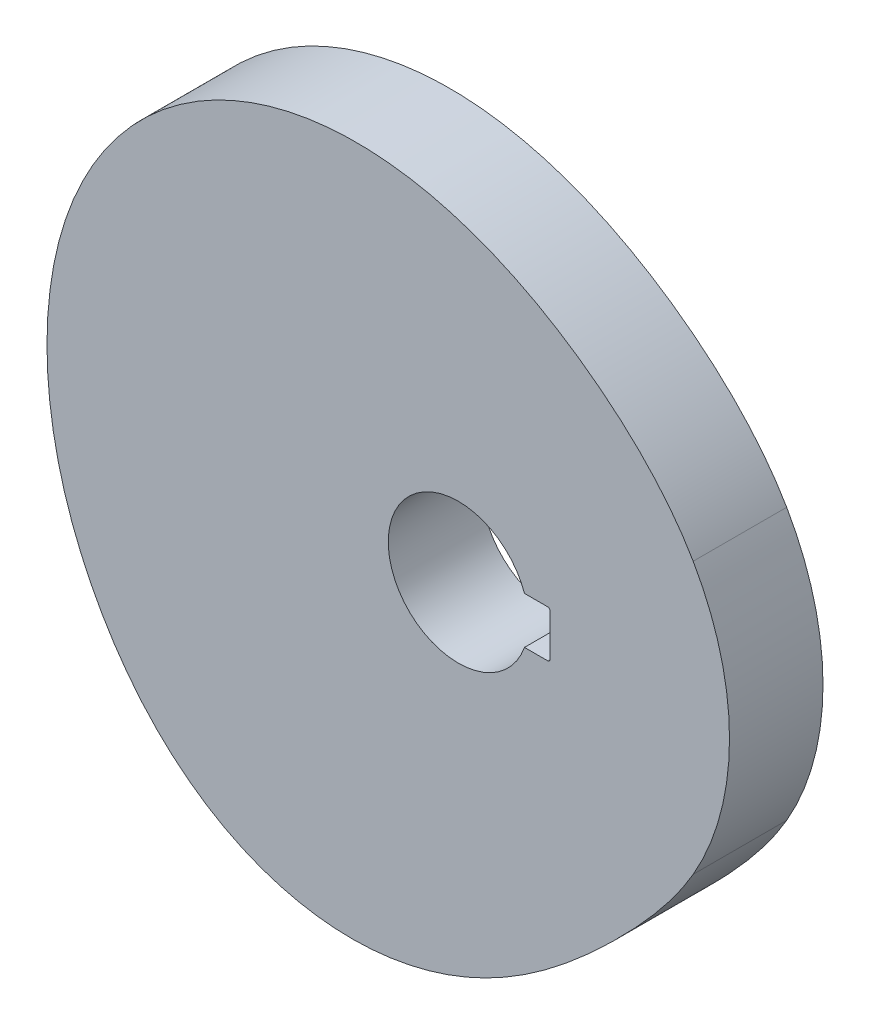
SolidWorks part; units mm, degrees
material "Plain Carbon Steel"
ref_plane "Front Plane" through (0, 0, 0) normal (0, 0, 1) x (1, 0, 0)
ref_plane "Top Plane" through (0, 0, 0) normal (0, 1, 0) x (1, 0, 0)
ref_plane "Right Plane" through (0, 0, 0) normal (1, 0, 0) x (0, 0, -1)
sketch "Displacement Sketch" plane through (0, 0, 0) normal (0, 0, 1) x (1, 0, 0)
  line L0 (0, 15) -> (0, 0) construction
  line L1 (0, 0) -> (47.1239, 0) construction
  line L2 (3.927, 0) -> (3.927, 15) construction
  line L3 (23.5619, 0) -> (23.5619, 15) construction
  line L4 (27.4889, 0) -> (27.4889, 15) construction
  line L5 (43.1969, 0) -> (43.1969, 15) construction
  line L6 (47.1239, 0) -> (47.1239, 15) construction
  line L7 (0, 0) -> (3.927, 0)
  line L8 (27.4889, 15) -> (23.5619, 15)
  line L9 (43.1969, 0) -> (47.1239, 0)
  spline S0 degree 4 poles (1.962, -0.0967) (2.0251, -0.0879) (2.1497, -0.0715) (2.3802, -0.0441) (2.7786, -0.0172) (3.1491, -0.0023) (3.8234, 0.0011) (4.1519, -0.0013) (4.7825, 0.0037) (5.2973, 0.0292) (5.8993, 0.0828) (6.4992, 0.198) (7.1843, 0.4092) (7.8229, 0.6945) (8.5028, 1.0958) (9.2434, 1.664) (10.1514, 2.5325) (11.1276, 3.6845) (12.1583, 5.0983) (13.2223, 6.6951) (14.2666, 8.3049) (15.3308, 9.9017) (16.361, 11.3155) (17.3382, 12.4675) (18.2447, 13.336) (18.9876, 13.9042) (19.6636, 14.3055) (20.2354, 14.5584) (20.6913, 14.7109) (21.0546, 14.8041) (21.3223, 14.8591) (21.5625, 14.8998) (21.7937, 14.9296) (22.0274, 14.9566) (22.3642, 14.9781) (22.6856, 14.9963) (23.3417, 15.0013) (23.6628, 14.9989) (24.3418, 15.0023) (24.7635, 15.0193) (25.1747, 15.049) (25.3985, 15.0791) (25.5259, 15.0967) knots 0 0 0 0 0 0.008159 0.016318 0.032637 0.048955 0.065274 0.0892 0.101163 0.113126 0.142767 0.163984 0.185201 0.206418 0.236195 0.268021 0.309045 0.372696 0.436348 0.5 0.563652 0.627304 0.690955 0.731979 0.763805 0.793582 0.814799 0.836016 0.846625 0.857233 0.864643 0.872053 0.879463 0.886874 0.898837 0.9108 0.934726 0.951045 0.967363 0.983682 1 1 1 1 1 construction
  spline S1 degree 4 poles (3.927, 0) (4.0838, 0) (4.3123, 0) (4.7825, 0.0037) (5.2973, 0.0292) (5.8993, 0.0828) (6.4992, 0.198) (7.1843, 0.4092) (7.8229, 0.6945) (8.5028, 1.0958) (9.2434, 1.664) (10.1514, 2.5325) (11.1276, 3.6845) (12.1583, 5.0983) (13.2223, 6.6951) (14.2666, 8.3049) (15.3308, 9.9017) (16.361, 11.3155) (17.3382, 12.4675) (18.2447, 13.336) (18.9876, 13.9042) (19.6636, 14.3055) (20.2354, 14.5584) (20.6913, 14.7109) (21.0546, 14.8041) (21.3223, 14.8591) (21.5625, 14.8998) (21.7937, 14.9296) (22.0274, 14.9566) (22.3642, 14.9781) (22.6856, 14.9963) (23.1748, 15) (23.4052, 15) (23.5619, 15) knots 0.065274 0.065274 0.065274 0.065274 0.065274 0.0892 0.101163 0.113126 0.142767 0.163984 0.185201 0.206418 0.236195 0.268021 0.309045 0.372696 0.436348 0.5 0.563652 0.627304 0.690955 0.731979 0.763805 0.793582 0.814799 0.836016 0.846625 0.857233 0.864643 0.872053 0.879463 0.886874 0.898837 0.9108 0.934726 0.934726 0.934726 0.934726 0.934726
  spline S2 degree 4 poles (25.917, 15.0967) (25.9672, 15.0879) (26.0664, 15.0716) (26.2503, 15.0442) (26.5692, 15.0173) (26.8684, 15.0023) (27.398, 14.9989) (27.6696, 15.0012) (28.1638, 14.9965) (28.4688, 14.9775) (28.7956, 14.949) (29.0691, 14.9044) (29.3652, 14.8416) (29.6303, 14.7623) (29.8895, 14.6683) (30.1363, 14.5572) (30.3781, 14.4298) (30.708, 14.2278) (31.1287, 13.9151) (31.7056, 13.3799) (32.4321, 12.5171) (33.1948, 11.3999) (33.9837, 10.0588) (34.759, 8.6207) (35.5133, 7.1717) (36.2737, 5.7258) (37.0683, 4.2981) (37.8437, 3.0586) (38.5964, 2.0494) (39.2866, 1.3197) (39.8479, 0.8516) (40.4053, 0.501) (40.8925, 0.2823) (41.3433, 0.149) (41.8164, 0.0573) (42.2412, 0.0166) (42.6103, 0.0017) (43.0977, -0.0005) (43.3551, 0.0006) (43.8251, -0.0023) (44.1115, -0.0173) (44.4386, -0.0442) (44.6184, -0.0716) (44.7185, -0.0879) (44.7693, -0.0967) knots 0 0 0 0 0 0.007472 0.014944 0.029888 0.044832 0.059777 0.081272 0.09202 0.102768 0.114604 0.126441 0.136767 0.147094 0.15742 0.167746 0.178072 0.188398 0.21612 0.247099 0.297177 0.359134 0.421092 0.48305 0.545008 0.606966 0.668924 0.730882 0.766656 0.797635 0.820922 0.841574 0.866069 0.878735 0.891402 0.915813 0.928018 0.940223 0.955168 0.970112 0.985056 0.992528 1 1 1 1 1 construction
  spline S3 degree 4 poles (27.4889, 15) (27.6137, 15) (27.7971, 15) (28.1638, 14.9965) (28.4688, 14.9775) (28.7956, 14.949) (29.0691, 14.9044) (29.3652, 14.8416) (29.6303, 14.7623) (29.8895, 14.6683) (30.1363, 14.5572) (30.3781, 14.4298) (30.708, 14.2278) (31.1287, 13.9151) (31.7056, 13.3799) (32.4321, 12.5171) (33.1948, 11.3999) (33.9837, 10.0588) (34.759, 8.6207) (35.5133, 7.1717) (36.2737, 5.7258) (37.0683, 4.2981) (37.8437, 3.0586) (38.5964, 2.0494) (39.2866, 1.3197) (39.8479, 0.8516) (40.4053, 0.501) (40.8925, 0.2823) (41.3433, 0.149) (41.8164, 0.0573) (42.2412, 0.0166) (42.6103, 0.0017) (42.9834, 0) (43.1261, 0) (43.1969, 0) knots 0.059777 0.059777 0.059777 0.059777 0.059777 0.081272 0.09202 0.102768 0.114604 0.126441 0.136767 0.147094 0.15742 0.167746 0.178072 0.188398 0.21612 0.247099 0.297177 0.359134 0.421092 0.48305 0.545008 0.606966 0.668924 0.730882 0.766656 0.797635 0.820922 0.841574 0.866069 0.878735 0.891402 0.915813 0.928018 0.940223 0.940223 0.940223 0.940223 0.940223
  dimension "D1" = 15
  dimension "D2" = 47.1239
  dimension "D3" = 3.927
  dimension "D4" = 19.635
  dimension "D5" = 3.927
  dimension "D6" = 15.708
  dimension "D7" = 3.927
sketch "Velocity Sketch" plane through (0, 0, 0) normal (0, 0, 1) x (1, 0, 0)
  line L0 (0, -15) -> (0, -65) construction
  line L1 (0, -40) -> (47.1239, -40) construction
  line L2 (3.927, -15) -> (3.927, -65) construction
  line L3 (23.5619, -15) -> (23.5619, -65) construction
  line L4 (27.4889, -15) -> (27.4889, -65) construction
  line L5 (43.1969, -15) -> (43.1969, -65) construction
  line L6 (47.1239, -15) -> (47.1239, -65) construction
  line L7 (0, -40) -> (3.927, -40)
  line L8 (23.5619, -40) -> (27.4889, -40)
  line L9 (43.1969, -40) -> (47.1239, -40)
  spline S0 degree 4 number of poles 82 (1.9635, -38.9057) -> (25.5254, -38.9057) construction
  spline S1 degree 4 poles (3.927, -40) (3.9591, -40) (4.0069, -39.9984) (4.0914, -39.9931) (4.2047, -39.9788) (4.3113, -39.9585) (4.4273, -39.9287) (4.5497, -39.8882) (4.6855, -39.8341) (4.8338, -39.7637) (5.0005, -39.6692) (5.2228, -39.5203) (5.4703, -39.3234) (5.7369, -39.0742) (6.0182, -38.7713) (6.2635, -38.4767) (6.4789, -38.1966) (6.7119, -37.8755) (6.9601, -37.5119) (7.2378, -37.08) (7.6188, -36.4531) (8.0578, -35.69) (8.695, -34.5334) (9.3923, -33.2428) (10.1106, -31.9631) (10.8521, -30.798) (11.4447, -29.9912) (12.0701, -29.306) (12.6823, -28.8165) (13.3594, -28.5265) (13.9982, -28.5224) (14.4931, -28.6816) (14.9938, -28.9673) (15.4821, -29.3759) (16.0352, -29.9801) (16.6301, -30.7877) (17.3726, -31.9534) (18.0917, -33.2337) (18.7893, -34.5249) (19.4267, -35.6821) (19.8657, -36.4456) (20.2468, -37.073) (20.5641, -37.567) (20.8732, -38.0148) (21.1744, -38.4151) (21.4671, -38.7672) (21.7491, -39.0713) (22.0564, -39.3589) (22.3514, -39.5861) (22.6045, -39.7396) (22.8026, -39.8338) (22.9386, -39.888) (23.0611, -39.9286) (23.1771, -39.9584) (23.2842, -39.9788) (23.3789, -39.9907) (23.4581, -39.9971) (23.5136, -39.9995) (23.5459, -40) (23.5619, -40) knots 0.064432 0.064432 0.064432 0.064432 0.064432 0.068544 0.0706 0.072656 0.076768 0.08088 0.083926 0.086973 0.093066 0.099159 0.105252 0.116762 0.128271 0.13978 0.15129 0.159464 0.167638 0.183987 0.200336 0.216684 0.249382 0.282079 0.347474 0.380171 0.412868 0.435887 0.458906 0.483278 0.499726 0.516191 0.528398 0.540605 0.563699 0.586794 0.619507 0.652221 0.717647 0.750361 0.783074 0.799431 0.815787 0.832144 0.8485 0.860048 0.871595 0.883143 0.89469 0.906897 0.913 0.916052 0.919104 0.92322 0.927336 0.929394 0.931452 0.93351 0.935568 0.935568 0.935568 0.935568 0.935568
  spline S2 degree 4 number of poles 99 (25.9181, -41.3678) -> (44.7677, -41.3678) construction
  spline S3 degree 4 number of poles 73 (27.4889, -40) -> (43.1969, -40)
  point P15 (23.5619, -40)
  point P27 (43.1969, -40)
  point P28 (3.927, -40)
  point P35 (27.4889, -40)
  dimension "D1" = 50
  dimension "D2" = 15
  dimension "D3" = 47.1239
sketch "Acceleration Sketch" plane through (0, 0, 0) normal (0, 0, 1) x (1, 0, 0)
  line L0 (0, -80) -> (0, -130) construction
  line L1 (0, -15) -> (0, -65) construction
  line L2 (3.927, -80) -> (3.927, -130) construction
  line L3 (23.5619, -80) -> (23.5619, -130) construction
  line L4 (27.4889, -80) -> (27.4889, -130) construction
  line L5 (43.1969, -80) -> (43.1969, -130) construction
  line L6 (47.1239, -80) -> (47.1239, -130) construction
  line L7 (0, -105) -> (47.1239, -105) construction
  spline S0 degree 4 number of poles 85 (2.572, -110.7775) -> (24.917, -99.2225) construction
  spline S1 degree 4 number of poles 69 (3.927, -105) -> (23.5619, -105)
  spline S2 degree 4 number of poles 85 (26.4484, -96.3102) -> (44.2375, -113.6898) construction
  spline S3 degree 4 number of poles 77 (27.4889, -105) -> (43.1969, -105)
  point P30 (3.927, -105)
  dimension "D1" = 15
sketch "Cam Profile Sketch" plane through (0, 0, 0) normal (0, 0, 1) x (1, 0, 0)
  line L0 (-49, 0) -> (-93, 0) construction
  line L1 (-49, 0) -> (-23.8853, 14.5) construction
  line L3 (-49, 0) -> (-87.1051, -22) construction
  line L4 (-23.8853, -14.5) -> (-49, 0) construction
  circle A1 centre (-49, 0) radius 29 construction
  arc A2 (-93, 0) -> (-87.1051, -22) centre (-49, 0) ccw
  arc A3 (-23.8853, -14.5) -> (-23.8853, 14.5) centre (-49, 0) ccw
  spline S0 degree 4 number of poles 84 (-21.0816, 7.4807) -> (-91.9863, -9.6611) construction
  spline S1 degree 4 poles (-23.8853, 14.5) (-23.9328, 14.5824) (-24.0277, 14.7445) (-24.2319, 15.0878) (-24.4645, 15.4634) (-24.7034, 15.8366) (-24.9512, 16.2123) (-25.2035, 16.5831) (-25.4607, 16.9499) (-25.7512, 17.3524) (-26.2677, 18.0453) (-27.1324, 19.1368) (-28.4165, 20.6093) (-30.1456, 22.3683) (-31.9522, 24.0003) (-33.682, 25.4157) (-35.2829, 26.6203) (-36.7346, 27.637) (-38.214, 28.6) (-39.7256, 29.5117) (-41.2684, 30.3695) (-43.2348, 31.3707) (-45.6528, 32.452) (-48.5535, 33.523) (-51.6032, 34.3581) (-54.3423, 34.8797) (-57.1097, 35.211) (-59.8951, 35.3457) (-63.056, 35.2217) (-66.5557, 34.7132) (-69.9807, 33.8313) (-73.2889, 32.5802) (-76.4387, 30.9712) (-79.4088, 29.0105) (-82.1582, 26.7166) (-84.6496, 24.1145) (-86.8505, 21.2354) (-88.7264, 18.1351) (-90.2072, 14.9786) (-91.2012, 12.1859) (-91.847, 9.8314) (-92.2209, 8.1094) (-92.439, 6.9089) (-92.5993, 5.859) (-92.7156, 4.9622) (-92.7998, 4.1755) (-92.8596, 3.4999) (-92.9013, 2.9365) (-92.9298, 2.4854) (-92.9534, 2.0327) (-92.9723, 1.5812) (-92.9864, 1.1389) (-92.9957, 0.6708) (-92.9992, 0.2901) (-93, 0.0959) (-93, 0) knots 0.066188 0.066188 0.066188 0.066188 0.066188 0.070099 0.07401 0.07792 0.081831 0.085742 0.089653 0.093564 0.097475 0.103059 0.11981 0.142146 0.165611 0.189076 0.204719 0.220116 0.235513 0.25091 0.266306 0.281703 0.2971 0.327893 0.358686 0.38948 0.407291 0.425102 0.455895 0.486688 0.517482 0.548275 0.579069 0.609862 0.640655 0.672207 0.70376 0.735312 0.766864 0.798416 0.82521 0.838607 0.852004 0.859892 0.86778 0.875668 0.883556 0.8875 0.891444 0.895388 0.899332 0.903276 0.90722 0.911164 0.915108 0.915108 0.915108 0.915108 0.915108
  spline S2 degree 4 number of poles 81 (-21.5114, -8.9316) -> (-90.4641, -14.9011) construction
  spline S3 degree 4 poles (-23.8853, -14.5) (-23.9228, -14.565) (-23.9986, -14.695) (-24.1533, -14.9565) (-24.3405, -15.2639) (-24.5245, -15.5577) (-24.7154, -15.8558) (-24.9096, -16.152) (-25.204, -16.5908) (-25.5555, -17.0963) (-26.07, -17.8075) (-26.6555, -18.5744) (-27.2016, -19.2598) (-27.9845, -20.2063) (-28.905, -21.2718) (-29.9727, -22.445) (-31.1919, -23.7204) (-32.3132, -24.8484) (-33.3264, -25.8344) (-34.356, -26.8033) (-35.4027, -27.7536) (-36.4677, -28.6835) (-37.5521, -29.5906) (-38.6574, -30.4723) (-40.0665, -31.5389) (-41.5142, -32.5534) (-43.2999, -33.6987) (-45.4952, -34.9391) (-47.7646, -36.0414) (-50.4458, -37.085) (-53.2075, -37.8928) (-55.9852, -38.4418) (-58.8021, -38.7298) (-61.634, -38.7457) (-64.4538, -38.4832) (-67.3037, -37.9274) (-69.7768, -37.1729) (-71.8775, -36.3239) (-73.6249, -35.4667) (-75.324, -34.5176) (-76.9536, -33.4513) (-78.5066, -32.2766) (-79.9784, -31.0034) (-80.9649, -30.0639) (-81.7785, -29.2267) (-82.4351, -28.5089) (-82.9475, -27.9232) (-83.4441, -27.3299) (-83.925, -26.73) (-84.391, -26.1233) (-84.8413, -25.5121) (-85.2807, -24.8903) (-85.7062, -24.2635) (-86.123, -23.6232) (-86.4733, -23.0634) (-86.7658, -22.58) (-86.9827, -22.2109) (-87.0648, -22.0699) (-87.1051, -22) knots 0.065589 0.065589 0.065589 0.065589 0.065589 0.069408 0.073227 0.077046 0.080865 0.084684 0.088503 0.092322 0.103716 0.111291 0.126441 0.134017 0.141592 0.16438 0.187294 0.202569 0.217845 0.233121 0.248396 0.263672 0.278948 0.294223 0.309499 0.324775 0.355326 0.370602 0.401153 0.433708 0.464259 0.49481 0.525362 0.555913 0.586464 0.617016 0.647567 0.6812 0.698016 0.714832 0.731649 0.765281 0.782098 0.798914 0.81573 0.824138 0.832546 0.840955 0.849363 0.857574 0.865785 0.873997 0.882208 0.890419 0.898631 0.906842 0.910948 0.915054 0.915054 0.915054 0.915054 0.915054
  dimension "D2" = 29
  dimension "D1" = 49
  dimension "D3" = 44
  dimension "D4" = 30
  dimension "D6" = 30
  dimension "D7" = 30
  dimension "D8" = 180
extrude "Boss-Extrude1" add sketch "Cam Profile Sketch" along normal mid plane 10 contours S1 A2 S3 A3
sketch "Sketch2" plane through (0, 0, 0) normal (0, 0, 1) x (1, 0, 0)
  circle A0 centre (-49, 0) radius 7.5
  dimension "D1" = 15
extrude "Cut-Extrude2" cut sketch "Sketch2" against normal up to next and the other way up to next
sketch "Sketch3" plane through (0, 0, 0) normal (0, 0, 1) x (1, 0, 0)
  line L0 (-49, 0) -> (-41.5, 0) construction
  line L2 (-41.9289, 2.5) -> (-39.2, 2.5)
  line L3 (-41.9289, 2.5) -> (-41.9289, -2.5)
  line L4 (-41.9289, -2.5) -> (-39.2, -2.5)
  line L5 (-39.2, 2.5) -> (-39.2, -2.5)
  circle A0 centre (-49, 0) radius 7.5 construction
  dimension "D1" = 5
  dimension "D2" = 2.3
extrude "Cut-Extrude3" cut sketch "Sketch3" against normal up to next and the other way up to next
fillet "Fillet1" radius 0.25 2 edges at (-39.2, -2.5, 0) (-39.2, 2.5, 0)
sketch "Sketch6" plane through (0, 0, 0) normal (0, 0, 1) x (1, 0, 0)
  arc A4 (-14.359, -20) -> (-14.359, 20) centre (-49, 0) ccw
  arc A6 (-14.359, -20) -> (-14.359, 20) centre (-49, 0) ccw construction
  spline S2 degree 3 poles (-104, 0) (-104, -9.7106) (-101.4867, -19.0904) (-96.6314, -27.5) knots 0 0 0 0 1 1 1 1 weights 1 0.977284 0.977284 1
  spline S3 degree 3 poles (-104, 0) (-104, -9.7106) (-101.4867, -19.0904) (-96.6314, -27.5) knots 0 0 0 0 1 1 1 1 weights 1 0.977284 0.977284 1
  spline S4 degree 3 poles (-2121.3509, -2107.8884) (-90.1041, -268.0393) (38.8532, -41.6264) (-20.5996, 28.4116) (-22.4507, 30.2678) (-24.9339, 32.4444) (-25.4387, 32.8721) (-26.4578, 33.7074) (-26.9729, 34.1158) (-28.5344, 35.3143) (-29.5968, 36.0777) (-32.8466, 38.2639) (-35.096, 39.5839) (-38.6055, 41.3389) (-39.7981, 41.886) (-41.6241, 42.6453) (-42.2401, 42.8885) (-43.4792, 43.3515) (-44.1013, 43.5708) (-47.2243, 44.6062) (-49.7632, 45.239) (-53.6363, 45.8756) (-54.9381, 46.0356) (-57.5645, 46.2456) (-58.895, 46.2951) (-62.8479, 46.27) (-65.4489, 46.0259) (-69.2986, 45.3166) (-70.5732, 45.0228) (-72.4716, 44.493) (-73.1022, 44.3015) (-74.3588, 43.8881) (-74.9855, 43.6658) (-78.0732, 42.4898) (-80.4238, 41.3359) (-83.7745, 39.2932) (-84.8621, 38.5601) (-86.9774, 36.9869) (-88.0088, 36.143) (-90.9518, 33.4994) (-92.7313, 31.5775) (-95.1366, 28.464) (-95.8941, 27.3876) (-96.9631, 25.7141) (-97.3081, 25.1465) (-97.9694, 24.0026) (-98.2864, 23.425) (-99.8056, 20.5097) (-100.8105, 18.0901) (-101.8163, 14.9617) (-102.0048, 14.3308) (-102.3568, 13.0586) (-102.5205, 12.4162) (-102.9719, 10.4812) (-103.2193, 9.185) (-136.6485, -212.174) (1276.4183, -601.8103) (-3010.0616, -323.1715) knots -2.072484 -2.072484 -2.072484 -2.072484 0.0625 0.0625 0.125 0.125 0.140625 0.140625 0.15625 0.15625 0.1875 0.1875 0.25 0.25 0.28125 0.28125 0.296875 0.296875 0.3125 0.3125 0.375 0.375 0.40625 0.40625 0.4375 0.4375 0.5 0.5 0.53125 0.53125 0.546875 0.546875 0.5625 0.5625 0.625 0.625 0.65625 0.65625 0.6875 0.6875 0.75 0.75 0.78125 0.78125 0.796875 0.796875 0.8125 0.8125 0.875 0.875 0.890625 0.890625 0.90625 0.90625 0.9375 0.9375 6.218529 6.218529 6.218529 6.218529 only from (-14.359, 20) to (-104, 0)
  spline S5 degree 3 poles (-2669.4706, -1511.9471) (347.9627, 724.0401) (-201.4987, 75.5733) (-88.246, -38.3286) (-87.4685, -39.057) (-85.8573, -40.4573) (-85.0312, -41.1228) (-82.492, -43.0154) (-80.7182, -44.1392) (-77.9326, -45.6129) (-76.9833, -46.0686) (-75.5269, -46.6973) (-75.036, -46.8976) (-74.0433, -47.2796) (-73.5402, -47.4616) (-71.0112, -48.3187) (-68.96, -48.8314) (-64.8037, -49.5242) (-62.6986, -49.7043) (-60.0329, -49.7174) (-59.4973, -49.7092) (-58.4318, -49.6719) (-57.9009, -49.6427) (-56.3137, -49.5242) (-55.2629, -49.404) (-52.1315, -48.9244) (-50.0719, -48.446) (-47.0233, -47.4984) (-46.0126, -47.1432) (-44.0327, -46.3685) (-43.06, -45.9479) (-40.1903, -44.5927) (-38.3418, -43.5645) (-35.6544, -41.8576) (-34.7712, -41.2599) (-33.0389, -40.0196) (-32.1924, -39.3789) (-29.7036, -37.4036) (-28.1117, -36.0161) (-25.027, -33.1371) (-23.5326, -31.6474) (-20.6447, -28.562) (-19.2514, -26.9647) (30.4783, 36.9799) (-58.8139, 192.9555) (-2354.1483, 1850.1458) knots -4.584283 -4.584283 -4.584283 -4.584283 0.125 0.125 0.15625 0.15625 0.1875 0.1875 0.25 0.25 0.28125 0.28125 0.296875 0.296875 0.3125 0.3125 0.375 0.375 0.4375 0.4375 0.453125 0.453125 0.46875 0.46875 0.5 0.5 0.5625 0.5625 0.59375 0.59375 0.625 0.625 0.6875 0.6875 0.71875 0.71875 0.75 0.75 0.8125 0.8125 0.875 0.875 0.9375 0.9375 3.249827 3.249827 3.249827 3.249827 only from (-96.6314, -27.5) to (-14.359, -20)
  spline S6 degree 3 poles (-14.359, 20) (-15.6869, 22.2999) (-17.2178, 24.4276) (-20.5996, 28.4116) (-22.4507, 30.2678) (-24.9339, 32.4444) (-25.4387, 32.8721) (-26.4578, 33.7074) (-26.9729, 34.1158) (-28.5344, 35.3143) (-29.5968, 36.0777) (-32.8466, 38.2639) (-35.096, 39.5839) (-38.6055, 41.3389) (-39.7981, 41.886) (-41.6241, 42.6453) (-42.2401, 42.8885) (-43.4792, 43.3515) (-44.1013, 43.5708) (-47.2243, 44.6062) (-49.7632, 45.239) (-53.6363, 45.8756) (-54.9381, 46.0356) (-57.5645, 46.2456) (-58.895, 46.2951) (-62.8479, 46.27) (-65.4489, 46.0259) (-69.2986, 45.3166) (-70.5732, 45.0228) (-72.4716, 44.493) (-73.1022, 44.3015) (-74.3588, 43.8881) (-74.9855, 43.6658) (-78.0732, 42.4898) (-80.4238, 41.3359) (-83.7745, 39.2932) (-84.8621, 38.5601) (-86.9774, 36.9869) (-88.0088, 36.143) (-90.9518, 33.4994) (-92.7313, 31.5775) (-95.1366, 28.464) (-95.8941, 27.3876) (-96.9631, 25.7141) (-97.3081, 25.1465) (-97.9694, 24.0026) (-98.2864, 23.425) (-99.8056, 20.5097) (-100.8105, 18.0901) (-101.8163, 14.9617) (-102.0048, 14.3308) (-102.3568, 13.0586) (-102.5205, 12.4162) (-102.9719, 10.4812) (-103.2193, 9.185) (-103.8093, 5.2785) (-104, 2.6504) (-104, 0) knots 0 0 0 0 0.0625 0.0625 0.125 0.125 0.140625 0.140625 0.15625 0.15625 0.1875 0.1875 0.25 0.25 0.28125 0.28125 0.296875 0.296875 0.3125 0.3125 0.375 0.375 0.40625 0.40625 0.4375 0.4375 0.5 0.5 0.53125 0.53125 0.546875 0.546875 0.5625 0.5625 0.625 0.625 0.65625 0.65625 0.6875 0.6875 0.75 0.75 0.78125 0.78125 0.796875 0.796875 0.8125 0.8125 0.875 0.875 0.890625 0.890625 0.90625 0.90625 0.9375 0.9375 1 1 1 1 construction
  spline S7 degree 3 poles (-96.6314, -27.5) (-94.4988, -31.1938) (-91.9789, -34.5743) (-88.246, -38.3286) (-87.4685, -39.057) (-85.8573, -40.4573) (-85.0312, -41.1228) (-82.492, -43.0154) (-80.7182, -44.1392) (-77.9326, -45.6129) (-76.9833, -46.0686) (-75.5269, -46.6973) (-75.036, -46.8976) (-74.0433, -47.2796) (-73.5402, -47.4616) (-71.0112, -48.3187) (-68.96, -48.8314) (-64.8037, -49.5242) (-62.6986, -49.7043) (-60.0329, -49.7174) (-59.4973, -49.7092) (-58.4318, -49.6719) (-57.9009, -49.6427) (-56.3137, -49.5242) (-55.2629, -49.404) (-52.1315, -48.9244) (-50.0719, -48.446) (-47.0233, -47.4984) (-46.0126, -47.1432) (-44.0327, -46.3685) (-43.06, -45.9479) (-40.1903, -44.5927) (-38.3418, -43.5645) (-35.6544, -41.8576) (-34.7712, -41.2599) (-33.0389, -40.0196) (-32.1924, -39.3789) (-29.7036, -37.4036) (-28.1117, -36.0161) (-25.027, -33.1371) (-23.5326, -31.6474) (-20.6447, -28.562) (-19.2514, -26.9647) (-16.6339, -23.5989) (-15.4257, -21.8476) (-14.359, -20) knots 0 0 0 0 0.125 0.125 0.15625 0.15625 0.1875 0.1875 0.25 0.25 0.28125 0.28125 0.296875 0.296875 0.3125 0.3125 0.375 0.375 0.4375 0.4375 0.453125 0.453125 0.46875 0.46875 0.5 0.5 0.5625 0.5625 0.59375 0.59375 0.625 0.625 0.6875 0.6875 0.71875 0.71875 0.75 0.75 0.8125 0.8125 0.875 0.875 0.9375 0.9375 1 1 1 1 construction
  dimension "D1" = 11
sketch3d "3DSketch1"
  arc A0 (-23.8853, 14.5, 0) -> (-23.8853, -14.5, 0) centre (-49, 0, 0) ccw
  arc A1 (-23.8853, 14.5, 0) -> (-23.8853, -14.5, 0) centre (-49, 0, 0) ccw
  arc A2 (-87.1051, -22, 0) -> (-93, 0, 0) centre (-49, 0, 0) ccw
  arc A3 (-87.1051, -22, 0) -> (-93, 0, 0) centre (-49, 0, 0) ccw
  spline S0 degree 4 poles (-1086.34, 1709.6276, 0) (-62.8727, -63.5271, 0) (-89.259, -18.1595, 0) (-87.6062, -21.1912, 0) (-86.4733, -23.0634, 0) (-86.123, -23.6232, 0) (-85.7062, -24.2635, 0) (-85.2807, -24.8903, 0) (-84.8413, -25.5121, 0) (-84.391, -26.1233, 0) (-83.925, -26.73, 0) (-83.4441, -27.3299, 0) (-82.9475, -27.9232, 0) (-82.4351, -28.5089, 0) (-81.7785, -29.2267, 0) (-80.9649, -30.0639, 0) (-79.9784, -31.0034, 0) (-78.5066, -32.2766, 0) (-76.9536, -33.4513, 0) (-75.324, -34.5176, 0) (-73.6249, -35.4667, 0) (-71.8775, -36.3239, 0) (-69.7768, -37.1729, 0) (-67.3037, -37.9274, 0) (-64.4538, -38.4832, 0) (-61.634, -38.7457, 0) (-58.8021, -38.7298, 0) (-55.9852, -38.4418, 0) (-53.2075, -37.8928, 0) (-50.4458, -37.085, 0) (-47.7646, -36.0414, 0) (-45.4952, -34.9391, 0) (-43.2999, -33.6987, 0) (-41.5142, -32.5534, 0) (-40.0665, -31.5389, 0) (-38.6574, -30.4723, 0) (-37.5521, -29.5906, 0) (-36.4677, -28.6835, 0) (-35.4027, -27.7536, 0) (-34.356, -26.8033, 0) (-33.3264, -25.8344, 0) (-32.3132, -24.8484, 0) (-31.1919, -23.7204, 0) (-29.9727, -22.445, 0) (-28.905, -21.2718, 0) (-27.9845, -20.2063, 0) (-27.2016, -19.2598, 0) (-26.6555, -18.5744, 0) (-26.07, -17.8075, 0) (-25.5555, -17.0963, 0) (-25.204, -16.5908, 0) (-24.9096, -16.152, 0) (-24.7154, -15.8558, 0) (-24.5245, -15.5577, 0) (-24.3405, -15.2639, 0) (-23.3608, -13.6549, 0) (-21.7979, -10.7579, 0) (-48.252, -56.0842, 0) (975.2221, 1717.4251, 0) knots -0.005181 -0.005181 -0.005181 -0.005181 -0.005181 0.069695 0.0738 0.082012 0.090223 0.098435 0.106646 0.114857 0.123069 0.13128 0.139688 0.148096 0.156504 0.164913 0.181729 0.198545 0.215361 0.248994 0.26581 0.282627 0.299443 0.333075 0.363627 0.394178 0.42473 0.455281 0.485832 0.516384 0.546935 0.57949 0.610041 0.625317 0.655868 0.671144 0.686419 0.701695 0.716971 0.732246 0.747522 0.762798 0.778073 0.793349 0.816263 0.839051 0.846626 0.854201 0.869352 0.876927 0.888321 0.89214 0.895959 0.899778 0.903597 0.907416 0.911235 0.979723 0.979723 0.979723 0.979723 0.979723 only from (-87.1051, -22, 0) to (-23.8853, -14.5, 0)
  spline S1 degree 4 poles (-87.1051, -22, 0) (-87.0648, -22.0699, 0) (-86.9827, -22.2109, 0) (-86.7658, -22.58, 0) (-86.4733, -23.0634, 0) (-86.123, -23.6232, 0) (-85.7062, -24.2635, 0) (-85.2807, -24.8903, 0) (-84.8413, -25.5121, 0) (-84.391, -26.1233, 0) (-83.925, -26.73, 0) (-83.4441, -27.3299, 0) (-82.9475, -27.9232, 0) (-82.4351, -28.5089, 0) (-81.7785, -29.2267, 0) (-80.9649, -30.0639, 0) (-79.9784, -31.0034, 0) (-78.5066, -32.2766, 0) (-76.9536, -33.4513, 0) (-75.324, -34.5176, 0) (-73.6249, -35.4667, 0) (-71.8775, -36.3239, 0) (-69.7768, -37.1729, 0) (-67.3037, -37.9274, 0) (-64.4538, -38.4832, 0) (-61.634, -38.7457, 0) (-58.8021, -38.7298, 0) (-55.9852, -38.4418, 0) (-53.2075, -37.8928, 0) (-50.4458, -37.085, 0) (-47.7646, -36.0414, 0) (-45.4952, -34.9391, 0) (-43.2999, -33.6987, 0) (-41.5142, -32.5534, 0) (-40.0665, -31.5389, 0) (-38.6574, -30.4723, 0) (-37.5521, -29.5906, 0) (-36.4677, -28.6835, 0) (-35.4027, -27.7536, 0) (-34.356, -26.8033, 0) (-33.3264, -25.8344, 0) (-32.3132, -24.8484, 0) (-31.1919, -23.7204, 0) (-29.9727, -22.445, 0) (-28.905, -21.2718, 0) (-27.9845, -20.2063, 0) (-27.2016, -19.2598, 0) (-26.6555, -18.5744, 0) (-26.07, -17.8075, 0) (-25.5555, -17.0963, 0) (-25.204, -16.5908, 0) (-24.9096, -16.152, 0) (-24.7154, -15.8558, 0) (-24.5245, -15.5577, 0) (-24.3405, -15.2639, 0) (-24.1533, -14.9565, 0) (-23.9986, -14.695, 0) (-23.9228, -14.565, 0) (-23.8853, -14.5, 0) knots 0.065589 0.065589 0.065589 0.065589 0.065589 0.069695 0.0738 0.082012 0.090223 0.098435 0.106646 0.114857 0.123069 0.13128 0.139688 0.148096 0.156504 0.164913 0.181729 0.198545 0.215361 0.248994 0.26581 0.282627 0.299443 0.333075 0.363627 0.394178 0.42473 0.455281 0.485832 0.516384 0.546935 0.57949 0.610041 0.625317 0.655868 0.671144 0.686419 0.701695 0.716971 0.732246 0.747522 0.762798 0.778073 0.793349 0.816263 0.839051 0.846626 0.854201 0.869352 0.876927 0.888321 0.89214 0.895959 0.899778 0.903597 0.907416 0.911235 0.915054 0.915054 0.915054 0.915054 0.915054
  spline S2 degree 4 poles (-92.388, -1999.3106, 0) (-92.7043, 49.3254, 0) (-92.9299, -4.8344, 0) (-93.0346, -1.2733, 0) (-92.9864, 1.1389, 0) (-92.9723, 1.5812, 0) (-92.9534, 2.0327, 0) (-92.9298, 2.4854, 0) (-92.9013, 2.9365, 0) (-92.8596, 3.4999, 0) (-92.7998, 4.1755, 0) (-92.7156, 4.9622, 0) (-92.5993, 5.859, 0) (-92.439, 6.9089, 0) (-92.2209, 8.1094, 0) (-91.847, 9.8314, 0) (-91.2012, 12.1859, 0) (-90.2072, 14.9786, 0) (-88.7264, 18.1351, 0) (-86.8505, 21.2354, 0) (-84.6496, 24.1145, 0) (-82.1582, 26.7166, 0) (-79.4088, 29.0105, 0) (-76.4387, 30.9712, 0) (-73.2889, 32.5802, 0) (-69.9807, 33.8313, 0) (-66.5557, 34.7132, 0) (-63.056, 35.2217, 0) (-59.8951, 35.3457, 0) (-57.1097, 35.211, 0) (-54.3423, 34.8797, 0) (-51.6032, 34.3581, 0) (-48.5535, 33.523, 0) (-45.6528, 32.452, 0) (-43.2348, 31.3707, 0) (-41.2684, 30.3695, 0) (-39.7256, 29.5117, 0) (-38.214, 28.6, 0) (-36.7346, 27.637, 0) (-35.2829, 26.6203, 0) (-33.682, 25.4157, 0) (-31.9522, 24.0003, 0) (-30.1456, 22.3683, 0) (-28.4165, 20.6093, 0) (-27.1324, 19.1368, 0) (-26.2677, 18.0453, 0) (-25.7512, 17.3524, 0) (-25.4607, 16.9499, 0) (-25.2035, 16.5831, 0) (-24.9512, 16.2123, 0) (-24.7034, 15.8366, 0) (-24.4645, 15.4634, 0) (-23.3636, 13.6856, 0) (-21.2575, 9.7985, 0) (-51.3705, 61.3574, 0) (975.0524, -1717.3854, 0) knots 0.000668 0.000668 0.000668 0.000668 0.000668 0.070132 0.074076 0.07802 0.081964 0.085908 0.089852 0.093796 0.09774 0.105628 0.113516 0.121404 0.129292 0.142689 0.156086 0.18288 0.214432 0.245984 0.277536 0.309089 0.340641 0.371434 0.402227 0.433021 0.463814 0.494608 0.525401 0.556194 0.574005 0.591816 0.62261 0.653403 0.684196 0.699593 0.71499 0.730386 0.745783 0.76118 0.776576 0.79222 0.815685 0.83915 0.861486 0.878237 0.883821 0.887732 0.891643 0.895554 0.899465 0.903376 0.907286 0.911197 0.973512 0.973512 0.973512 0.973512 0.973512 only from (-93, 0, 0) to (-23.8853, 14.5, 0)
  spline S3 degree 4 poles (-93, 0, 0) (-93, 0.0959, 0) (-92.9992, 0.2901, 0) (-92.9957, 0.6708, 0) (-92.9864, 1.1389, 0) (-92.9723, 1.5812, 0) (-92.9534, 2.0327, 0) (-92.9298, 2.4854, 0) (-92.9013, 2.9365, 0) (-92.8596, 3.4999, 0) (-92.7998, 4.1755, 0) (-92.7156, 4.9622, 0) (-92.5993, 5.859, 0) (-92.439, 6.9089, 0) (-92.2209, 8.1094, 0) (-91.847, 9.8314, 0) (-91.2012, 12.1859, 0) (-90.2072, 14.9786, 0) (-88.7264, 18.1351, 0) (-86.8505, 21.2354, 0) (-84.6496, 24.1145, 0) (-82.1582, 26.7166, 0) (-79.4088, 29.0105, 0) (-76.4387, 30.9712, 0) (-73.2889, 32.5802, 0) (-69.9807, 33.8313, 0) (-66.5557, 34.7132, 0) (-63.056, 35.2217, 0) (-59.8951, 35.3457, 0) (-57.1097, 35.211, 0) (-54.3423, 34.8797, 0) (-51.6032, 34.3581, 0) (-48.5535, 33.523, 0) (-45.6528, 32.452, 0) (-43.2348, 31.3707, 0) (-41.2684, 30.3695, 0) (-39.7256, 29.5117, 0) (-38.214, 28.6, 0) (-36.7346, 27.637, 0) (-35.2829, 26.6203, 0) (-33.682, 25.4157, 0) (-31.9522, 24.0003, 0) (-30.1456, 22.3683, 0) (-28.4165, 20.6093, 0) (-27.1324, 19.1368, 0) (-26.2677, 18.0453, 0) (-25.7512, 17.3524, 0) (-25.4607, 16.9499, 0) (-25.2035, 16.5831, 0) (-24.9512, 16.2123, 0) (-24.7034, 15.8366, 0) (-24.4645, 15.4634, 0) (-24.2319, 15.0878, 0) (-24.0277, 14.7445, 0) (-23.9328, 14.5824, 0) (-23.8853, 14.5, 0) knots 0.066188 0.066188 0.066188 0.066188 0.066188 0.070132 0.074076 0.07802 0.081964 0.085908 0.089852 0.093796 0.09774 0.105628 0.113516 0.121404 0.129292 0.142689 0.156086 0.18288 0.214432 0.245984 0.277536 0.309089 0.340641 0.371434 0.402227 0.433021 0.463814 0.494608 0.525401 0.556194 0.574005 0.591816 0.62261 0.653403 0.684196 0.699593 0.71499 0.730386 0.745783 0.76118 0.776576 0.79222 0.815685 0.83915 0.861486 0.878237 0.883821 0.887732 0.891643 0.895554 0.899465 0.903376 0.907286 0.911197 0.915108 0.915108 0.915108 0.915108 0.915108
  point P4 (-49, 0, -29)
  point P5 (-49, 0, -29)
  point P8 (-49, 0, -44)
  point P9 (-49, 0, -44)
sketch "Sketch7" plane through (0, 0, 0) normal (0, 0, 1) x (1, 0, 0)
  arc A0 (-14.359, -20) -> (-14.359, 20) centre (-49, 0) ccw construction
  arc A2 (-14.359, -20) -> (-14.359, 20) centre (-49, 0) ccw
  arc A3 (-104, 0) -> (-96.6314, -27.5) centre (-49, 0) ccw
  arc A6 (-104, 0) -> (-96.6314, -27.5) centre (-49, 0) ccw
  arc A7 (-104, 0) -> (-96.6314, -27.5) centre (-49, 0) ccw
  spline S0 degree 3 poles (-3470.577, -2110.4352) (440.8098, 832.0201) (-210.5642, 84.6908) (-88.246, -38.3286) (-87.4685, -39.057) (-85.8573, -40.4573) (-85.0312, -41.1228) (-82.492, -43.0154) (-80.7182, -44.1392) (-77.9326, -45.6129) (-76.9833, -46.0686) (-75.5269, -46.6973) (-75.036, -46.8976) (-74.0433, -47.2796) (-73.5402, -47.4616) (-71.0112, -48.3187) (-68.96, -48.8314) (-64.8037, -49.5242) (-62.6986, -49.7043) (-60.0329, -49.7174) (-59.4973, -49.7092) (-58.4318, -49.6719) (-57.9009, -49.6427) (-56.3137, -49.5242) (-55.2629, -49.404) (-52.1315, -48.9244) (-50.0719, -48.446) (-47.0233, -47.4984) (-46.0126, -47.1432) (-44.0327, -46.3685) (-43.06, -45.9479) (-40.1903, -44.5927) (-38.3418, -43.5645) (-35.6544, -41.8576) (-34.7712, -41.2599) (-33.0389, -40.0196) (-32.1924, -39.3789) (-29.7036, -37.4036) (-28.1117, -36.0161) (-25.027, -33.1371) (-23.5326, -31.6474) (-20.6447, -28.562) (-19.2514, -26.9647) (35.6421, 43.6198) (-79.4253, 227.2893) (-3166.2825, 2433.2658) knots -4.963748 -4.963748 -4.963748 -4.963748 0.125 0.125 0.15625 0.15625 0.1875 0.1875 0.25 0.25 0.28125 0.28125 0.296875 0.296875 0.3125 0.3125 0.375 0.375 0.4375 0.4375 0.453125 0.453125 0.46875 0.46875 0.5 0.5 0.5625 0.5625 0.59375 0.59375 0.625 0.625 0.6875 0.6875 0.71875 0.71875 0.75 0.75 0.8125 0.8125 0.875 0.875 0.9375 0.9375 3.496424 3.496424 3.496424 3.496424 only from (-96.6314, -27.5) to (-14.359, -20) construction
  spline S1 degree 3 poles (-2864.4269, -2776.822) (-120.7917, -319.8603) (45.2182, -49.1245) (-20.5996, 28.4116) (-22.4507, 30.2678) (-24.9339, 32.4444) (-25.4387, 32.8721) (-26.4578, 33.7074) (-26.9729, 34.1158) (-28.5344, 35.3143) (-29.5968, 36.0777) (-32.8466, 38.2639) (-35.096, 39.5839) (-38.6055, 41.3389) (-39.7981, 41.886) (-41.6241, 42.6453) (-42.2401, 42.8885) (-43.4792, 43.3515) (-44.1013, 43.5708) (-47.2243, 44.6062) (-49.7632, 45.239) (-53.6363, 45.8756) (-54.9381, 46.0356) (-57.5645, 46.2456) (-58.895, 46.2951) (-62.8479, 46.27) (-65.4489, 46.0259) (-69.2986, 45.3166) (-70.5732, 45.0228) (-72.4716, 44.493) (-73.1022, 44.3015) (-74.3588, 43.8881) (-74.9855, 43.6658) (-78.0732, 42.4898) (-80.4238, 41.3359) (-83.7745, 39.2932) (-84.8621, 38.5601) (-86.9774, 36.9869) (-88.0088, 36.143) (-90.9518, 33.4994) (-92.7313, 31.5775) (-95.1366, 28.464) (-95.8941, 27.3876) (-96.9631, 25.7141) (-97.3081, 25.1465) (-97.9694, 24.0026) (-98.2864, 23.425) (-99.8056, 20.5097) (-100.8105, 18.0901) (-101.8163, 14.9617) (-102.0048, 14.3308) (-102.3568, 13.0586) (-102.5205, 12.4162) (-102.9719, 10.4812) (-103.2193, 9.185) (-138.9988, -227.7372) (1483.5265, -657.7714) (-4007.5779, -253.7285) knots -2.307743 -2.307743 -2.307743 -2.307743 0.0625 0.0625 0.125 0.125 0.140625 0.140625 0.15625 0.15625 0.1875 0.1875 0.25 0.25 0.28125 0.28125 0.296875 0.296875 0.3125 0.3125 0.375 0.375 0.40625 0.40625 0.4375 0.4375 0.5 0.5 0.53125 0.53125 0.546875 0.546875 0.5625 0.5625 0.625 0.625 0.65625 0.65625 0.6875 0.6875 0.75 0.75 0.78125 0.78125 0.796875 0.796875 0.8125 0.8125 0.875 0.875 0.890625 0.890625 0.90625 0.90625 0.9375 0.9375 6.592021 6.592021 6.592021 6.592021 only from (-14.359, 20) to (-104, 0) construction
  spline S2 degree 3 poles (-96.6314, -27.5) (-94.4988, -31.1938) (-91.9789, -34.5743) (-88.246, -38.3286) (-87.4685, -39.057) (-85.8573, -40.4573) (-85.0312, -41.1228) (-82.492, -43.0154) (-80.7182, -44.1392) (-77.9326, -45.6129) (-76.9833, -46.0686) (-75.5269, -46.6973) (-75.036, -46.8976) (-74.0433, -47.2796) (-73.5402, -47.4616) (-71.0112, -48.3187) (-68.96, -48.8314) (-64.8037, -49.5242) (-62.6986, -49.7043) (-60.0329, -49.7174) (-59.4973, -49.7092) (-58.4318, -49.6719) (-57.9009, -49.6427) (-56.3137, -49.5242) (-55.2629, -49.404) (-52.1315, -48.9244) (-50.0719, -48.446) (-47.0233, -47.4984) (-46.0126, -47.1432) (-44.0327, -46.3685) (-43.06, -45.9479) (-40.1903, -44.5927) (-38.3418, -43.5645) (-35.6544, -41.8576) (-34.7712, -41.2599) (-33.0389, -40.0196) (-32.1924, -39.3789) (-29.7036, -37.4036) (-28.1117, -36.0161) (-25.027, -33.1371) (-23.5326, -31.6474) (-20.6447, -28.562) (-19.2514, -26.9647) (-16.6339, -23.5989) (-15.4257, -21.8476) (-14.359, -20) knots 0 0 0 0 0.125 0.125 0.15625 0.15625 0.1875 0.1875 0.25 0.25 0.28125 0.28125 0.296875 0.296875 0.3125 0.3125 0.375 0.375 0.4375 0.4375 0.453125 0.453125 0.46875 0.46875 0.5 0.5 0.5625 0.5625 0.59375 0.59375 0.625 0.625 0.6875 0.6875 0.71875 0.71875 0.75 0.75 0.8125 0.8125 0.875 0.875 0.9375 0.9375 1 1 1 1
  spline S3 degree 3 poles (-14.359, 20) (-15.6869, 22.2999) (-17.2178, 24.4276) (-20.5996, 28.4116) (-22.4507, 30.2678) (-24.9339, 32.4444) (-25.4387, 32.8721) (-26.4578, 33.7074) (-26.9729, 34.1158) (-28.5344, 35.3143) (-29.5968, 36.0777) (-32.8466, 38.2639) (-35.096, 39.5839) (-38.6055, 41.3389) (-39.7981, 41.886) (-41.6241, 42.6453) (-42.2401, 42.8885) (-43.4792, 43.3515) (-44.1013, 43.5708) (-47.2243, 44.6062) (-49.7632, 45.239) (-53.6363, 45.8756) (-54.9381, 46.0356) (-57.5645, 46.2456) (-58.895, 46.2951) (-62.8479, 46.27) (-65.4489, 46.0259) (-69.2986, 45.3166) (-70.5732, 45.0228) (-72.4716, 44.493) (-73.1022, 44.3015) (-74.3588, 43.8881) (-74.9855, 43.6658) (-78.0732, 42.4898) (-80.4238, 41.3359) (-83.7745, 39.2932) (-84.8621, 38.5601) (-86.9774, 36.9869) (-88.0088, 36.143) (-90.9518, 33.4994) (-92.7313, 31.5775) (-95.1366, 28.464) (-95.8941, 27.3876) (-96.9631, 25.7141) (-97.3081, 25.1465) (-97.9694, 24.0026) (-98.2864, 23.425) (-99.8056, 20.5097) (-100.8105, 18.0901) (-101.8163, 14.9617) (-102.0048, 14.3308) (-102.3568, 13.0586) (-102.5205, 12.4162) (-102.9719, 10.4812) (-103.2193, 9.185) (-103.8093, 5.2785) (-104, 2.6504) (-104, 0) knots 0 0 0 0 0.0625 0.0625 0.125 0.125 0.140625 0.140625 0.15625 0.15625 0.1875 0.1875 0.25 0.25 0.28125 0.28125 0.296875 0.296875 0.3125 0.3125 0.375 0.375 0.40625 0.40625 0.4375 0.4375 0.5 0.5 0.53125 0.53125 0.546875 0.546875 0.5625 0.5625 0.625 0.625 0.65625 0.65625 0.6875 0.6875 0.75 0.75 0.78125 0.78125 0.796875 0.796875 0.8125 0.8125 0.875 0.875 0.890625 0.890625 0.90625 0.90625 0.9375 0.9375 1 1 1 1
  point P3 (-96.6314, -27.5)
  point P4 (0, 0)
  dimension "D1" = 11
equation "\"Dwell Angle 1\"= 30"
equation "\"Rise Angle\"= 150"
equation "\"Dwell Angle 2\"= 30"
equation "\"Return Angle\"= 120"
equation "\"Dwell Angle 3\"= 30"
equation "\"Prime Circle Radius\"= 40"
equation "\"Roller Radius\"= 11"
equation "\"Base Circle Radius\"= \"Prime Circle Radius\" - \"Roller Radius\""
equation "\"Lift\"= 15"
equation "\"D1@Displacement Sketch\" = \"Lift\""
equation "\"D2@Displacement Sketch\" = \"Lift\" * pi"
equation "\"Dwell Radians 1\"= \"Dwell Angle 1\" * pi / 180"
equation "\"Rise Radians\"= \"Rise Angle\" * pi / 180"
equation "\"Dwell Radians 2\"= \"Dwell Angle 2\" * pi / 180"
equation "\"Return Radians\"= \"Return Angle\" * pi / 180"
equation "\"Dwell Radian 3\"= \"Dwell Angle 3\" * pi / 180"
equation "\"D3@Displacement Sketch\"=\"Dwell Radians 1\" * \"Lift\" / 2"
equation "\"D4@Displacement Sketch\"=\"Rise Radians\" * \"Lift\" / 2"
equation "\"D5@Displacement Sketch\"=\"Dwell Radians 2\" * \"Lift\" / 2"
equation "\"D6@Displacement Sketch\"=\"Return Radians\" * \"Lift\" / 2"
equation "\"D7@Displacement Sketch\"=\"Dwell Radian 3\" * \"Lift\" / 2"
equation "\"D8@Cam Profile Sketch\" = \"Dwell Angle 1\" + \"Rise Angle\""
equation "\"D6@Cam Profile Sketch\" = \"Dwell Angle 2\""
equation "\"D1@Cam Profile Sketch\" = \"Base Circle Radius\" + 20"
equation "\"D1@Velocity Sketch\" = 50"
equation "\"D3@Velocity Sketch\" = 2 * pi * \"Lift\" / 2"
equation "\"D1@Sketch6\"=\"Roller Radius\""
equation "\"D1@Sketch7\"=\"Roller Radius\""
